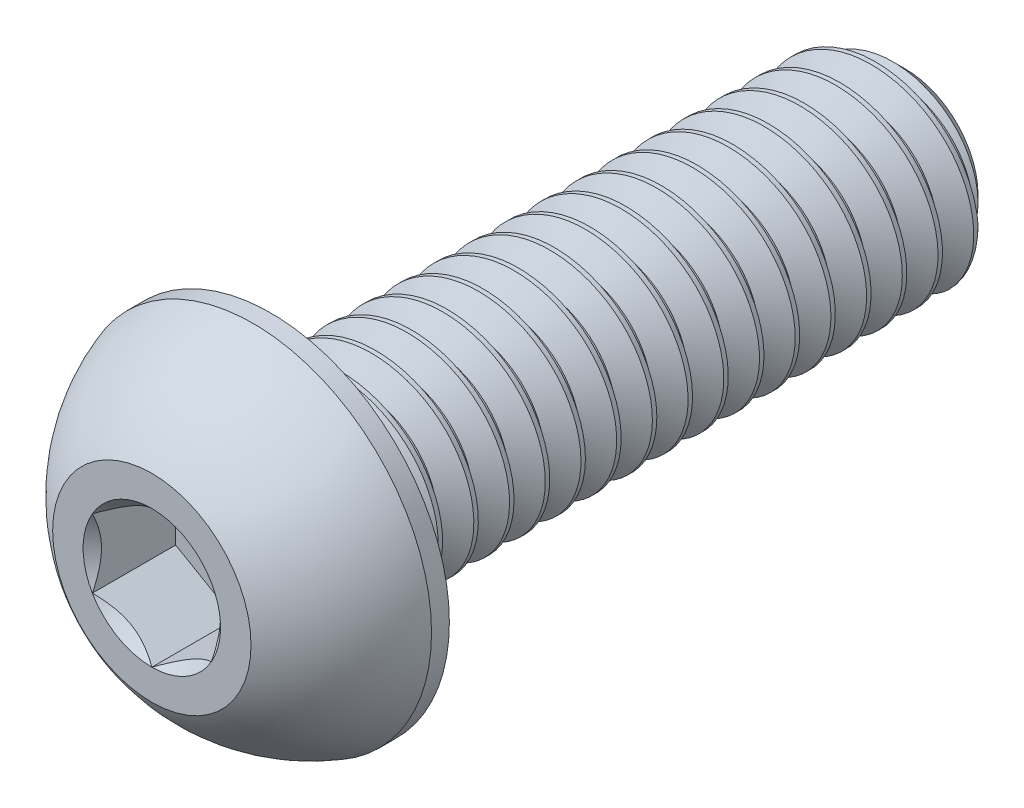
SolidWorks part; units mm, degrees
ref_plane "Front" through (0, 0, 0) normal (0, 0, 1) x (1, 0, 0)
ref_plane "Top" through (0, 0, 0) normal (0, 1, 0) x (1, 0, 0)
ref_plane "Right" through (0, 0, 0) normal (1, 0, 0) x (0, 0, -1)
sketch "Sketch1" plane through (0, 0, 0) normal (1, 0, 0) x (0, 0, -1)
  line L2 (1.5, 1.25) -> (9.5, 1.25)
  line L3 (9.5, 1.25) -> (9.5, 0)
  line L4 (9.5, 0) -> (1.5, 0)
  line L6 (1.275, 2.25) -> (1.5, 2.25) construction
  line L7 (9.5, 1.25) -> (9.5, -1.25) construction
  line L8 (0, 0) -> (1.5, 0) construction
  line L9 (1.5, 2.25) -> (1.5, -2.25) construction
  line L11 (1.5, 1.25) -> (1.5, 0)
  line L13 (0, 0.75) -> (0, -0.75) construction
  line L14 (0, 0.75) -> (0, 1.25) construction
  line L15 (9.4719, 1.2987) -> (9.6969, 0.909) construction
  line L16 (9.6969, 0.909) -> (9.9219, 1.2987) construction
  line L17 (9.9219, 1.2987) -> (9.4719, 1.2987) construction
  line L18 (9.5, 1.25) -> (9.8938, 1.25) construction
  line L19 (9.6969, 1.2987) -> (9.6969, 1.25) construction
  line L20 (9.6969, 1.25) -> (9.6969, 0.9577) construction
  line L21 (9.6969, 0.9577) -> (9.6969, 0.909) construction
  line L22 (9.6688, 0.9577) -> (9.725, 0.9577)
  line L23 (9.4859, 1.2744) -> (9.9078, 1.2744)
  line L24 (9.725, 0.9577) -> (9.9078, 1.2744)
  line L25 (9.6688, 0.9577) -> (9.4859, 1.2744)
  line L26 (9.1625, 1.25) -> (9.5, 0.9125)
  arc A3 (0, 1.25) -> (1.275, 2.25) centre (2.01, 0) cw construction
  point P29 (9.6969, 1.2744)
  point P30 (8.375, -1.25)
  dimension "D1" = 0.225
  dimension "Pitch" = 0.45
  dimension "D3" = 0.0563
  dimension "D2" = 0.3375
  dimension "D4" = 45
  dimension "D5" = 1.125
sketch "Sketch10" plane through (0, 0, 0) normal (1, 0, 0) x (0, 0, -1)
  line L0 (9.1625, 1.25) -> (9.5, 0.9125) construction
  line L1 (9.1625, 1.25) -> (9.5, 0.9125)
  line L4 (9.5, 1.25) -> (1.5, 1.25)
  line L5 (9.5, 0) -> (9.5, 1.25)
  line L6 (1.5, 0) -> (9.5, 0)
  line L7 (1.5, 1.25) -> (1.5, 0)
  line L8 (9.1625, 1.25) -> (1.5, 1.25)
  line L9 (9.5, 0) -> (9.5, 0.9125)
  line L10 (1.5, 0) -> (9.5, 0)
  line L11 (1.5, 1.25) -> (1.5, 0)
  dimension "D1" = 0
revolve "Revolve3" add sketch "Sketch10" angle 360 about L8
sketch "Sketch7" plane through (0, 0, 0) normal (1, 0, 0) x (0, 0, -1)
  line L6 (1.275, 2.25) -> (1.5, 2.25) construction
  line L8 (0, 0) -> (1.5, 0) construction
  line L11 (1.5, 2.25) -> (1.5, -2.25) construction
  line L12 (1.275, 2.25) -> (1.5, 2.25)
  line L13 (0, 0) -> (1.5, 0)
  line L14 (0, 0.75) -> (0, -0.75) construction
  line L15 (1.5, 2.25) -> (1.5, 0)
  line L16 (0, 1.25) -> (0, 0)
  arc A2 (1.275, 2.25) -> (0, 1.25) centre (2.01, 0) ccw construction
  arc A3 (1.275, 2.25) -> (0, 1.25) centre (2.01, 0) ccw
revolve "Revolve2" add sketch "Sketch7" angle 360 mid plane about L13
sketch "Sketch5" plane through (0, 0, 0) normal (0, 0, 1) x (1, 0, 0)
  line L1 (0.75, -0.433) -> (0.75, 0.433)
  line L2 (0.75, 0.433) -> (0, 0.866)
  line L3 (0, 0.866) -> (-0.75, 0.433)
  line L4 (-0.75, 0.433) -> (-0.75, -0.433)
  line L5 (-0.75, -0.433) -> (0, -0.866)
  line L6 (0, -0.866) -> (0.75, -0.433)
  circle A0 centre (0, 0) radius 0.75 construction
extrude "Cut-Extrude2" cut sketch "Sketch5" against normal blind 1.05
sketch "Sketch6" plane through (0, 0, 0) normal (0, 0, 1) x (1, 0, 0)
  circle A0 centre (0, 0) radius 0.866
extrude "Cut-Extrude3" cut sketch "Sketch6" against normal blind 1.05 draft 45
sketch "Sketch9" plane through (0, 0, -1.5) normal (0, 0, -1) x (-1, 0, 0)
  circle A0 centre (0, 0) radius 1.25 construction
  circle A4 centre (0, 0) radius 1.25
split "Split1" bodies to split 113 resulting bodies 123 124 split by face at (2.25, 0, -1.5)
sketch "Sketch11" plane through (0, 0, -9.5) normal (0, 0, -1) x (-1, 0, 0)
  circle A0 centre (0, 0) radius 1.25 construction
  circle A1 centre (0, 0) radius 1.25
curve "Helix/Spiral1" pitch 0.45 height 9.5 radius 1.25 centre (0, 0, -9.5) axis (0, 0, 1) start towards (0, 1, 0)
sketch "Sketch12" plane through (0, 0, 0) normal (1, 0, 0) x (0, 0, -1)
  line L0 (9.6688, 0.9577) -> (9.725, 0.9577) construction
  line L1 (9.725, 0.9577) -> (9.9078, 1.2744) construction
  line L2 (9.4859, 1.2744) -> (9.9078, 1.2744) construction
  line L3 (9.6688, 0.9577) -> (9.4859, 1.2744) construction
  line L4 (9.6688, 0.9577) -> (9.725, 0.9577)
  line L5 (9.725, 0.9577) -> (9.9078, 1.2744)
  line L6 (9.4859, 1.2744) -> (9.9078, 1.2744)
  line L7 (9.6688, 0.9577) -> (9.4859, 1.2744)
sweep "Cut-Sweep2" cut profiles "Sketch12" path "Helix/Spiral1" align with end faces yes
extrude "Boss-Extrude1" add sketch "Sketch9" along normal blind 10 draft 45
equation "\"D1@Cut-Extrude2\" = \"Head Ht@Sketch1\" * .7"
equation "\"D1@Sketch1\" = \"Head Ht@Sketch1\" * .15"
equation "\"D1@Cut-Extrude3\" = \"D1@Cut-Extrude2\""
equation "\"D3@Sketch1\" = \"Pitch@Sketch1\" / 8"
equation "\"D2@Sketch1\"=\"Pitch@Sketch1\"*0.75"
equation "\"D3@Helix/Spiral1\" = \"Lg@Sketch1\" + \"Head Ht@Sketch1\""
equation "\"D4@Helix/Spiral1\"=\"pitch@sketch1\""
equation "\"D5@Sketch1\"=\"Pitch@Sketch1\"*2.5"
